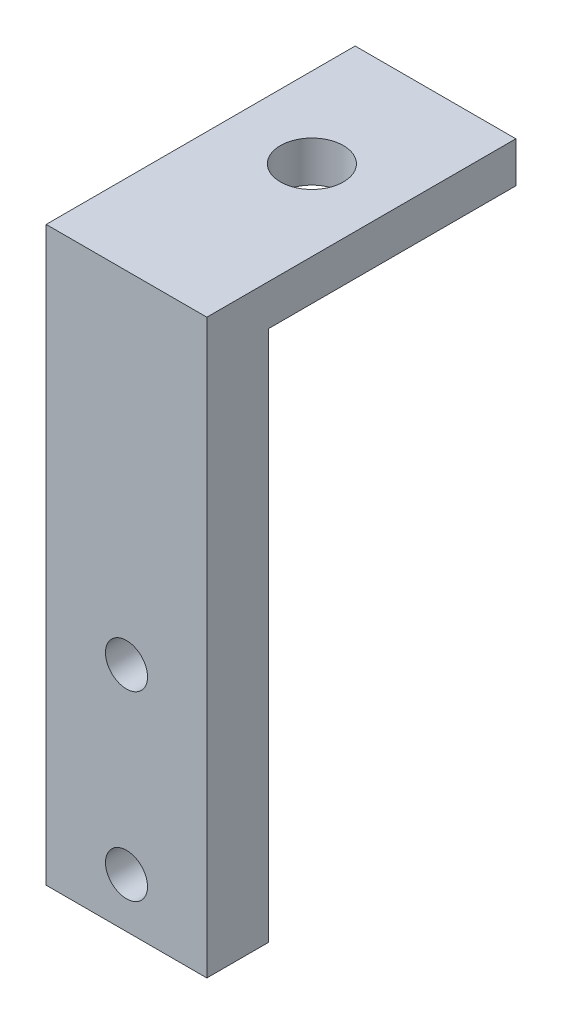
SolidWorks part; units mm, degrees
ref_plane "Front Plane" through (0, 0, 0) normal (0, 0, 1) x (1, 0, 0)
ref_plane "Top Plane" through (0, 0, 0) normal (0, 1, 0) x (1, 0, 0)
ref_plane "Right Plane" through (0, 0, 0) normal (1, 0, 0) x (0, 0, -1)
sketch "Sketch1" plane through (0, 0, 0) normal (1, 0, 0) x (0, 0, -1)
  line L0 (0, 0) -> (0, 46.3)
  line L1 (0, 46.3) -> (25, 46.3)
  line L2 (25, 46.3) -> (25, 43)
  line L3 (25, 43) -> (5, 43)
  line L4 (5, 43) -> (5, 0)
  line L5 (5, 0) -> (0, 0)
  dimension "D1" = 3.3
  dimension "D2" = 5
  dimension "D3" = 43
  dimension "D4" = 20
extrude "Boss-Extrude1" add sketch "Sketch1" along normal blind 13
sketch "Sketch2" plane through (0, 0, -5) normal (0, 0, -1) x (-1, 0, 0)
  line L0 (-13, 0) -> (0, 0) construction
  line L1 (-6.5, 0) -> (-6.5, 18.7) construction
  circle A0 centre (-6.5, 18.7) radius 1.7
  circle A1 centre (-6.5, 4) radius 1.7
  dimension "D3" = 3.4
  dimension "D1" = 14.7
  dimension "D2" = 4
extrude "Cut-Extrude1" cut sketch "Sketch2" against normal through all
sketch "Sketch3" plane through (0, 46.3, 0) normal (0, 1, 0) x (1, 0, 0)
  line L0 (6.5, 25) -> (6.5, 15) construction
  line L1 (13, 25) -> (0, 25) construction
  line L2 (0, 25) -> (0, 5) construction
  line L3 (0, 25) -> (0, 0) construction
  circle A0 centre (6.5, 15) radius 2.55
  point P10 (0, 15)
  dimension "D2" = 5.1
  dimension "D1" = 20
extrude "Cut-Extrude2" cut sketch "Sketch3" against normal through all
